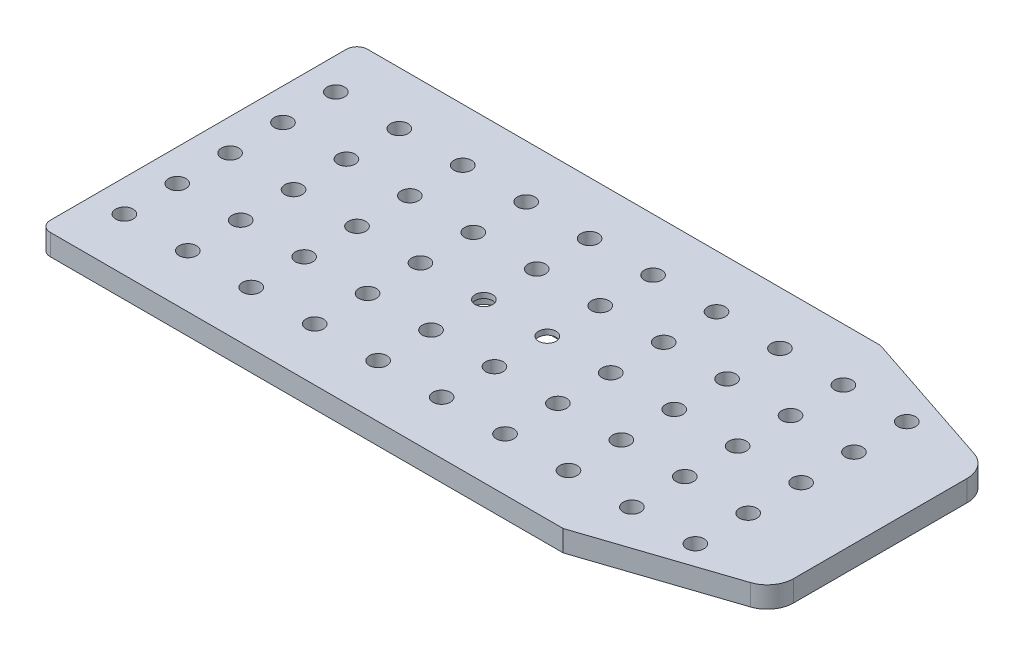
SolidWorks part; units mm, degrees
ref_plane "Front Plane" through (0, 0, 0) normal (0, 0, 1) x (1, 0, 0)
ref_plane "Top Plane" through (0, 0, 0) normal (0, 1, 0) x (1, 0, 0)
ref_plane "Right Plane" through (0, 0, 0) normal (1, 0, 0) x (0, 0, -1)
sketch "Sketch1" plane through (0, 0, 0) normal (0, 1, 0) x (1, 0, 0)
  line L0 (-75, 25) -> (-22.5, 25)
  line L1 (-75, 25) -> (75, 25)
  line L2 (-75, 25) -> (-75, -25)
  line L3 (-75, -25) -> (75, -25)
  line L4 (75, 25) -> (75, -25)
  line L5 (-75, 25) -> (75, -25) construction
  line L6 (-75, -25) -> (75, 25) construction
  line L7 (-75, 0) -> (-51.8537, 0) construction
  line L8 (-75, 25) -> (75, 25)
  line L9 (-75, 25) -> (-75, 45)
  line L10 (-75, 45) -> (75, 45)
  line L11 (75, 25) -> (75, 45)
  line L12 (-75, -45) -> (75, -45)
  line L13 (75, -25) -> (75, -45)
  line L14 (-75, -25) -> (75, -25)
  line L15 (-75, -25) -> (-75, -45)
  line L17 (-75, -25) -> (75, -25)
  line L18 (-75, -25) -> (-75, -45)
  line L19 (-75, -45) -> (75, -45)
  line L20 (75, -25) -> (75, -45)
  point P0 (0, 0)
  dimension "D1" = 50
  dimension "D2" = 150
  dimension "D3" = 20
extrude "Boss-Extrude1" add sketch "Sketch1" along normal blind 4 contours L1 L11 L10 L9 L0 | L4 L1 L0 L2 L3 | L3 L15 L12 L13 region at (0, 0, -35) region at (0, 0, 0) region at (0, 0, 35)
fillet "Fillet1" radius 5 4 edges at (-75, 2, -45) (75, 2, -45) (75, 2, 45) (-75, 2, 45)
sketch "Sketch2" plane through (0, 4, 0) normal (0, 1, 0) x (1, 0, 0)
  line L0 (-75, 0) -> (-25, 0) construction
  line L1 (-75, -40) -> (-75, 40) construction
  line L3 (-70, 20) -> (-30, 20)
  line L4 (-70, 20) -> (-70, -20)
  line L5 (-70, -20) -> (-30, -20)
  line L6 (-30, 20) -> (-30, -20)
  line L7 (-70, 20) -> (-30, -20) construction
  line L8 (-70, -20) -> (-30, 20) construction
  circle A0 centre (-70, 20) radius 1.65
  circle A1 centre (-60, 20) radius 1.65
  circle A2 centre (-50, 20) radius 1.65
  circle A3 centre (-40, 20) radius 1.65
  circle A4 centre (-30, 20) radius 1.65
  circle A5 centre (-60, 10) radius 1.65
  circle A6 centre (-50, 10) radius 1.65
  circle A7 centre (-40, 10) radius 1.65
  circle A8 centre (-30, 10) radius 1.65
  circle A9 centre (-60, 0) radius 1.65
  circle A10 centre (-50, 0) radius 1.65
  circle A11 centre (-40, 0) radius 1.65
  circle A12 centre (-30, 0) radius 1.65
  circle A13 centre (-60, -10) radius 1.65
  circle A14 centre (-50, -10) radius 1.65
  circle A15 centre (-40, -10) radius 1.65
  circle A16 centre (-30, -10) radius 1.65
  circle A17 centre (-60, -20) radius 1.65
  circle A18 centre (-50, -20) radius 1.65
  circle A19 centre (-40, -20) radius 1.65
  circle A20 centre (-30, -20) radius 1.65
  circle A21 centre (-70, 10) radius 1.65
  circle A22 centre (-70, 0) radius 1.65
  circle A23 centre (-70, -10) radius 1.65
  circle A24 centre (-70, -20) radius 1.65
  circle A25 centre (-18, 20) radius 1.65
  circle A26 centre (-18, 10) radius 1.65
  circle A27 centre (-18, 0) radius 1.65
  circle A28 centre (-18, -10) radius 1.65
  circle A29 centre (-18, -20) radius 1.65
  circle A30 centre (-6, 20) radius 1.65
  circle A31 centre (-6, 10) radius 1.65
  circle A32 centre (-6, 0) radius 1.65
  circle A33 centre (-6, -10) radius 1.65
  circle A34 centre (-6, -20) radius 1.65
  circle A35 centre (6, 20) radius 1.65
  circle A36 centre (6, 10) radius 1.65
  circle A37 centre (6, 0) radius 1.65
  circle A38 centre (6, -10) radius 1.65
  circle A39 centre (6, -20) radius 1.65
  circle A40 centre (18, 20) radius 1.65
  circle A41 centre (18, 10) radius 1.65
  circle A42 centre (18, 0) radius 1.65
  circle A43 centre (18, -10) radius 1.65
  circle A44 centre (18, -20) radius 1.65
  circle A45 centre (30, 20) radius 1.65
  circle A46 centre (30, 10) radius 1.65
  circle A47 centre (30, 0) radius 1.65
  circle A48 centre (30, -10) radius 1.65
  circle A49 centre (30, -20) radius 1.65
  circle A50 centre (42, 20) radius 1.65
  circle A51 centre (42, 10) radius 1.65
  circle A52 centre (42, 0) radius 1.65
  circle A53 centre (42, -10) radius 1.65
  circle A54 centre (42, -20) radius 1.65
  circle A55 centre (54, 20) radius 1.65
  circle A56 centre (54, 10) radius 1.65
  circle A57 centre (54, 0) radius 1.65
  circle A58 centre (54, -10) radius 1.65
  circle A59 centre (54, -20) radius 1.65
  point P5 (-50, 0)
  dimension "D4" = 5
  dimension "D1" = 40
  dimension "D2" = 40
  dimension "D3" = 50
  dimension "D5" = 5
  dimension "D6" = 8
extrude "Cut-Extrude1" cut sketch "Sketch2" against normal mid plane 8 contours A6 | A5 | L4 A21 | L4 A21 | L6 A12 | L6 A12 | A11 | A10 | A9 | L4 A22 | L4 A22 | L4 A23 | L4 A23 | A13 | A14 | A15 | L6 A16 | L6 A16 | L5 A20 L6 | L6 A20 L5 | L5 A19 | L5 A19 | L5 A18 | L5 A18 | L5 A17 | L5 A17 | A29 | A28 | A27 | A26 | A25 | A30 | A35 | A40 | A31 | A36 | A41 | A46 | A51 | A56 | A57 | A58 | A59 | A54 | A52 | A48 | A47 | A49 | A44 | A34 | A33 | A32 | A37 | A38 | A39 | A43 | A42 | A45 | A50 | A55 | A1 | A2 | A3 | A4 | A8 | A7 | A24 | A53 | A0 region at (-69.2997, 4, -10) region at (-70.7003, 4, -10) region at (-69.2997, 4, 0) region at (-70.7003, 4, 0) region at (-69.2997, 4, 10) region at (-70.7003, 4, 10) region at (-60, 4, 19.2997) region at (-60, 4, 20.7003) region at (-29.2997, 4, 0) region at (-30.7003, 4, 0) region at (-50, 4, 19.2997) region at (-50, 4, 20.7003) region at (-29.2997, 4, 10) region at (-30.7003, 4, 10) region at (-40, 4, 19.2997) region at (-40, 4, 20.7003) region at (-29.7666, 4, 20.2334) region at (-30.7003, 4, 19.2997) region at (-60, 4, -10) region at (-50, 4, -10) region at (-60, 4, 0) region at (-50, 4, 0) region at (-40, 4, 0) region at (-60, 4, 10) region at (-50, 4, 10) region at (-40, 4, 10) region at (-18, 4, -20) region at (-18, 4, -10) region at (-18, 4, 0) region at (-18, 4, 10) region at (-18, 4, 20) region at (-6, 4, -20) region at (-6, 4, -10) region at (-6, 4, 0) region at (-6, 4, 10) region at (-6, 4, 20) region at (6, 4, -20) region at (6, 4, -10) region at (6, 4, 0) region at (6, 4, 10) region at (6, 4, 20) region at (18, 4, -20) region at (18, 4, -10) region at (18, 4, 0) region at (18, 4, 10) region at (18, 4, 20) region at (30, 4, -20) region at (30, 4, -10) region at (30, 4, 0) region at (30, 4, 10) region at (30, 4, 20) region at (42, 4, -20) region at (42, 4, -10) region at (42, 4, 0) region at (42, 4, 20) region at (54, 4, -20) region at (54, 4, -10) region at (54, 4, 0) region at (54, 4, 10) region at (54, 4, 20)
sketch "Sketch3" plane through (0, 4, 0) normal (0, 1, 0) x (1, 0, 0)
  circle A0 centre (-70, 20) radius 2
extrude "Cut-Extrude2" cut sketch "Sketch3" along normal mid plane 8
sketch "Sketch4" plane through (0, 4, 0) normal (0, 1, 0) x (1, 0, 0)
  line L0 (-75, -30) -> (-25, -30)
  line L9 (-75, 30) -> (-25, -30) construction
  line L10 (-75, -30) -> (-25, 30) construction
  line L11 (-25, -45) -> (-25, -30)
  line L12 (-70, -45) -> (70, -45) construction
  line L13 (-75, 0) -> (-54.7832, 0) construction
  line L14 (-25, -30) -> (-87.892, -30)
  line L15 (-25, -30) -> (-25, -45)
  line L16 (-25, -45) -> (-87.892, -45)
  line L17 (-87.892, -30) -> (-87.892, -45)
  line L18 (-25, 45) -> (-87.892, 45)
  line L19 (-87.892, 30) -> (-87.892, 45)
  line L20 (-25, 30) -> (-87.892, 30)
  line L21 (-25, 30) -> (-25, 45)
  line L22 (-75, 0) -> (-23.7735, 0)
  point P6 (-50, 0)
  dimension "D1" = 50
  dimension "D2" = 30
  dimension "D3" = 30
extrude "Cut-Extrude3" cut sketch "Sketch4" against normal blind 33 contours L21 L18 L19 L20 | L14 L17 L16 L11 L0 region at (-56.446, 4, 37.5) region at (-56.446, 4, -37.5)
fillet "Fillet2" radius 5 2 edges at (-25, 2, 45) (-25, 2, -45)
sketch "Sketch14" plane through (0, 4, 0) normal (0, 1, 0) x (1, 0, 0)
  line L0 (75, 0) -> (59.2452, 0)
  line L2 (75, -40) -> (75, 40) construction
  line L3 (25, 33) -> (25, 45)
  line L4 (65, 39) -> (35, 39) construction
  line L5 (-20, 45) -> (70, 45) construction
  line L6 (65, 42) -> (35, 42)
  line L7 (25, 39) -> (-25, 39)
  line L8 (-25, 30) -> (-25, 40) construction
  line L11 (-15, 39) -> (15, 39) construction
  line L14 (-15, 42) -> (15, 42)
  line L17 (-15, 36) -> (15, 36)
  line L20 (-25, -30) -> (75, -30)
  line L21 (65, 36) -> (35, 36)
  line L30 (65, -39) -> (35, -39) construction
  line L33 (65, -42) -> (35, -42)
  line L34 (65, -36) -> (35, -36)
  line L35 (-15, -39) -> (15, -39) construction
  line L36 (-15, -42) -> (15, -42)
  line L37 (-15, -36) -> (15, -36)
  line L38 (-25, 30) -> (75, 30)
  arc A16 (-15, 42) -> (-15, 36) centre (-15, 39) ccw
  arc A17 (15, 36) -> (15, 42) centre (15, 39) ccw
  arc A20 (65, -42) -> (65, -36) centre (65, -39) ccw
  arc A21 (35, -36) -> (35, -42) centre (35, -39) ccw
  arc A22 (-15, -42) -> (-15, -36) centre (-15, -39) cw
  arc A23 (15, -36) -> (15, -42) centre (15, -39) cw
  arc A24 (65, 42) -> (65, 36) centre (65, 39) cw
  arc A25 (35, 36) -> (35, 42) centre (35, 39) cw
  point P17 (0, 39)
  point P24 (50, 39)
  point P31 (50, -39)
  point P38 (0, -39)
  dimension "D2" = 30
  dimension "D1" = 6
  dimension "D3" = 3
  dimension "D4" = 50
  dimension "D5" = 12
  dimension "D6" = 30
extrude "Cut-Extrude4" cut sketch "Sketch14" against normal blind 3 contours L17 A17 L7 A16 | L7 A17 L14 A16 | A25 L21 A24 L6 | A23 L37 A22 L36 | L34 A21 L33 A20 region at (50, 4, -39) region at (0, 4, -37.5308) region at (0, 4, -40.4692) region at (50, 4, 39) region at (0, 4, 39)
sketch "Sketch15" plane through (0, 4, 0) normal (0, 1, 0) x (1, 0, 0)
  line L0 (-25, 30) -> (75, 30)
  line L1 (75, -40) -> (75, 40) construction
  line L2 (-25, -30) -> (75, -30)
  line L3 (75, 0) -> (105, 0) construction
  line L4 (105, 20) -> (105, -20)
  line L5 (75, 30) -> (105, 20)
  line L6 (105, -20) -> (75, -30)
  line L7 (75, 30) -> (75, -30)
  point P14 (105, 0)
  dimension "D1" = 30
  dimension "D2" = 40
extrude "Boss-Extrude2" add sketch "Sketch15" against normal blind 4 contours L3 L7 L6 L4 | L7 L3 L4 L5 region at (89, 4, -12.6667) region at (89, 4, 12.6667)
fillet "Fillet3" radius 5 2 edges at (105, 2, -20) (105, 2, 20)
sketch "Sketch16" plane through (0, 4, 0) normal (0, 1, 0) x (1, 0, 0)
  line L0 (54, 0) -> (105, 0)
  line L1 (105, 16.3962) -> (105, -16.3962) construction
  line L2 (54, 0) -> (66, 0)
  circle A0 centre (66, 0) radius 1.65
  circle A1 centre (78, 0) radius 1.65
  circle A2 centre (90, 0) radius 1.65
  circle A3 centre (78, 10) radius 1.65
  circle A4 centre (90, 10) radius 1.65
  circle A5 centre (78, 20) radius 1.65
  circle A6 centre (90, 20) radius 1.65
  circle A7 centre (66, 10) radius 1.65
  circle A8 centre (66, 20) radius 1.65
  circle A9 centre (66, -10) radius 1.65
  circle A10 centre (78, -10) radius 1.65
  circle A11 centre (90, -10) radius 1.65
  circle A12 centre (66, -20) radius 1.65
  circle A13 centre (78, -20) radius 1.65
  circle A14 centre (90, -20) radius 1.65
  dimension "D2" = 3
  dimension "D1" = 12
  dimension "D3" = 3
  dimension "D4" = 3
extrude "Cut-Extrude5" cut sketch "Sketch16" against normal blind 3 contours A5 | A6 | A7 | A3 | A4 | A11 | A14 | A8 | A2 | A1 | A0 | A9 | A12 | A13 | A10 region at (78, 4, -10) region at (90, 4, -10) region at (78, 4, -20) region at (90, 4, -20) region at (66, 4, -10) region at (90, 4, 10) region at (90, 4, 20)
sketch "Sketch18" plane through (0, 0, 0) normal (0, -1, 0) x (-1, 0, 0)
  line L0 (-30, 0) -> (-42, 0) construction
  line L1 (-30, -4.5) -> (-42, -4.5)
  line L2 (-30, 4.5) -> (-42, 4.5)
  arc A0 (-30, -4.5) -> (-30, 4.5) centre (-30, 0) ccw
  arc A1 (-42, 4.5) -> (-42, -4.5) centre (-42, 0) ccw
  point P4 (-36, 0)
  dimension "D1" = 9
extrude "Cut-Extrude6" cut sketch "Sketch18" against normal blind 3
fillet "Fillet4" radius 5 2 edges at (-75, 2, 30) (-75, 2, -30)
sketch "Sketch19" plane through (0, 4, 0) normal (0, 1, 0) x (1, 0, 0)
  line L1 (-25, 30) -> (84.5217, 30)
  line L2 (-25, 30) -> (-25, 54.4245)
  line L3 (-25, 54.4245) -> (84.5217, 54.4245)
  line L4 (84.5217, 30) -> (84.5217, 54.4245)
  line L5 (-25, -30) -> (79.1165, -30)
  line L6 (-25, -30) -> (-25, -60.5752)
  line L7 (-25, -60.5752) -> (79.1165, -60.5752)
  line L8 (79.1165, -30) -> (79.1165, -60.5752)
extrude "Cut-Extrude7" cut sketch "Sketch19" against normal blind 20
sketch "Sketch20" plane through (0, 4, 0) normal (0, 1, 0) x (1, 0, 0)
  line L0 (-30, 0) -> (-18, 0)
  line L6 (-87.5589, -42.8626) -> (-24, -42.8626)
  line L7 (-87.5589, -42.8626) -> (-87.5589, 38.2889)
  line L8 (-87.5589, 38.2889) -> (-24, 38.2889)
  line L9 (-24, -42.8626) -> (-24, 38.2889)
extrude "Cut-Extrude8" cut sketch "Sketch20" against normal blind 10 contours L6 L9 L8 L7 region at (-55.7795, 4, 2.2868)
fillet "Fillet5" radius 2 2 edges at (-24, 2, -30) (-24, 2, 30)
